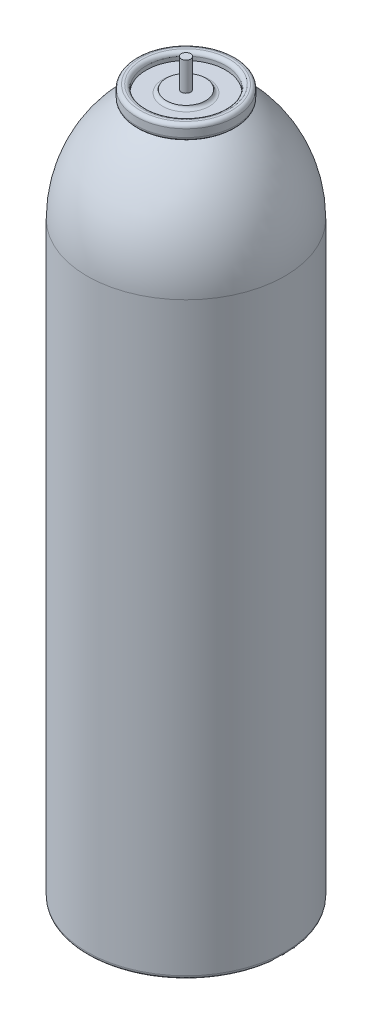
SolidWorks part; units mm, degrees
ref_plane "Front Plane" through (0, 0, 0) normal (0, 0, 1) x (1, 0, 0)
ref_plane "Top Plane" through (0, 0, 0) normal (0, 1, 0) x (1, 0, 0)
ref_plane "Right Plane" through (0, 0, 0) normal (1, 0, 0) x (0, 0, -1)
sketch "Sketch1" plane through (0, 0, 0) normal (0, 0, 1) x (1, 0, 0)
  line L0 (0, -195.9804) -> (0, 326.7985) construction
  line L1 (0, 0) -> (33.3375, 0)
  line L2 (0, 238.125) -> (16.6624, 238.125)
  line L3 (0, 233.045) -> (16.6624, 233.045)
  line L4 (16.6624, 238.125) -> (16.6624, 233.045)
  line L5 (33.3375, 0) -> (33.3375, 198.7137)
  line L6 (0, 0) -> (0, 238.125)
  arc A0 (33.3375, 198.7137) -> (15.37, 233.045) centre (-8.4455, 198.7137) ccw
  dimension "D5" = 41.783
  dimension "D1" = 33.3375
  dimension "D2" = 238.125
  dimension "D3" = 16.6624
  dimension "D4" = 5.08
  dimension "D6" = 15.37
revolve "Revolve1" add sketch "Sketch1" angle 360 about L0 region at (16.3885, 113.8956, 0) region at (8.3312, 235.585, 0)
sketch "Sketch2" plane through (0, 238.125, 0) normal (0, 1, 0) x (1, 0, 0)
  circle A0 centre (0, 0) radius 13.3604
  circle A1 centre (0, 0) radius 16.6624 construction
  dimension "D1" = 3.302
extrude "Cut-Extrude1" cut sketch "Sketch2" against normal blind 2.54 contours A0
sketch "Sketch3" plane through (0, 235.585, 0) normal (0, 1, 0) x (1, 0, 0)
  circle A0 centre (0, 0) radius 6.6112
  dimension "D1" = 13.2223
extrude "Boss-Extrude1" add sketch "Sketch3" along normal blind 1.016
sketch "Sketch4" plane through (0, 236.601, 0) normal (0, 1, 0) x (1, 0, 0)
  circle A0 centre (0, 0) radius 1.5875
  dimension "D1" = 3.175
extrude "Boss-Extrude2" add sketch "Sketch4" along normal blind 9.652
sketch "Sketch8" plane through (0, 0, 0) normal (0, -1, 0) x (1, 0, 0)
  circle A0 centre (0, 0) radius 27.8888
  circle A1 centre (0, 0) radius 33.3375 construction
  dimension "D1" = 5.4487
extrude "Cut-Extrude2" cut sketch "Sketch8" against normal blind 7.112
fillet "Fillet1" radius 5.08 1 edges at (0, 7.112, -27.8888)
fillet "Fillet4" radius 1.27 2 edges at (0, 233.045, -16.6624) (0, 238.125, -16.6624)
fillet "Fillet5" radius 1.27 1 edges at (0, 238.125, 13.3604)
fillet "Fillet6" radius 1.27 1 edges at (0, 0, -33.3375)
fillet "Fillet7" radius 1.27 1 edges at (0, 0, -27.8888)
fillet "Fillet8" radius 1.27 1 edges at (0, 235.585, 6.6112)
